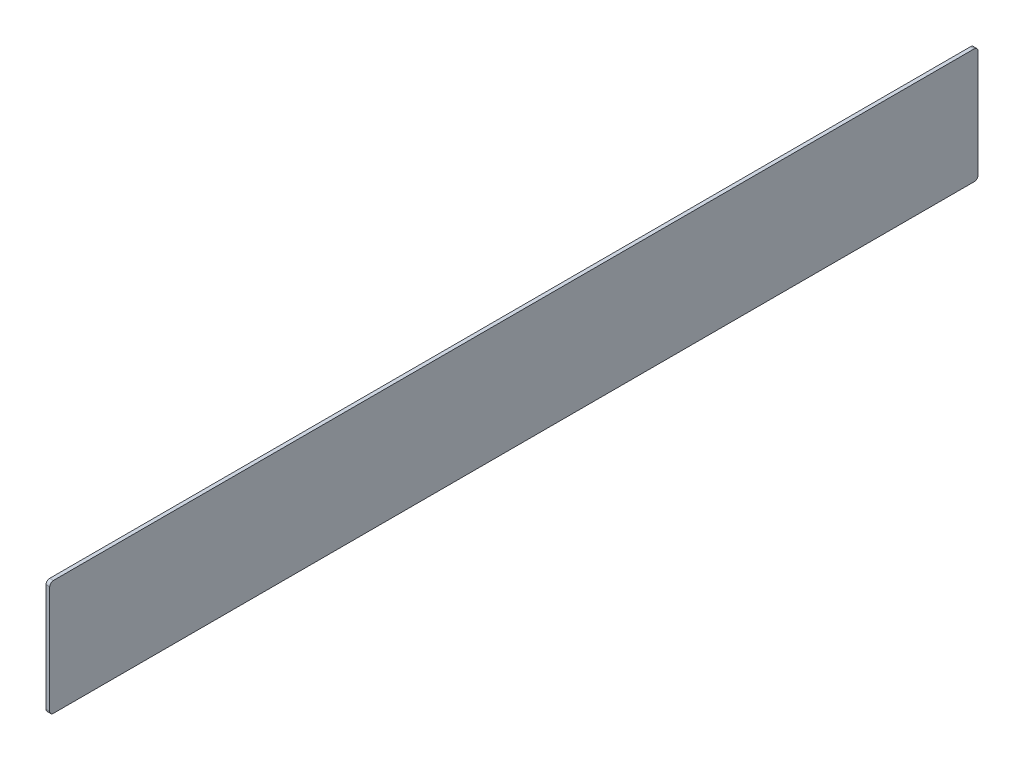
SolidWorks part; units mm, degrees
ref_plane "Front Plane" through (0, 0, 0) normal (0, 0, 1) x (1, 0, 0)
ref_plane "Top Plane" through (0, 0, 0) normal (0, 1, 0) x (1, 0, 0)
ref_plane "Right Plane" through (0, 0, 0) normal (1, 0, 0) x (0, 0, -1)
sketch "Sketch1" plane through (0, 0, 0) normal (1, 0, 0) x (0, 0, -1)
  line L1 (-269.9468, -78.2926) -> (230.0532, -78.2926)
  line L2 (-269.9468, -78.2926) -> (-269.9468, -140.2926)
  line L3 (-269.9468, -140.2926) -> (230.0532, -140.2926)
  line L4 (230.0532, -78.2926) -> (230.0532, -140.2926)
  dimension "D1" = 500
  dimension "D2" = 62
extrude "Boss-Extrude1" add sketch "Sketch1" along normal blind 2
fillet "Fillet1" radius 2 4 edges at (1, -140.2926, -230.0532) (1, -78.2926, -230.0532) (1, -140.2926, 269.9468) (1, -78.2926, 269.9468)
